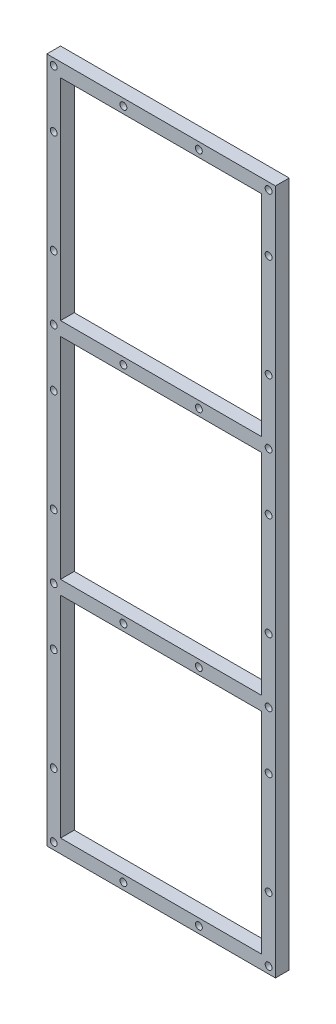
SolidWorks part; units mm, degrees
ref_plane "Front Plane" through (0, 0, 0) normal (0, 0, 1) x (1, 0, 0)
ref_plane "Top Plane" through (0, 0, 0) normal (0, 1, 0) x (1, 0, 0)
ref_plane "Right Plane" through (0, 0, 0) normal (1, 0, 0) x (0, 0, -1)
sketch "Sketch1" plane through (0, 0, 0) normal (0, 0, 1) x (1, 0, 0)
  line L0 (44, 144) -> (44, 52)
  line L9 (-50, -150) -> (50, -150)
  line L10 (-50, -150) -> (-50, 150)
  line L11 (-50, 150) -> (50, 150)
  line L12 (50, -150) -> (50, 150)
  line L15 (-44, -144) -> (44, -144)
  line L16 (-44, -144) -> (-44, -52)
  line L17 (-44, 144) -> (44, 144)
  line L21 (-44, 52) -> (44, 52)
  line L23 (-44, 46) -> (44, 46)
  line L25 (-44, -46) -> (44, -46)
  line L27 (-44, -52) -> (44, -52)
  line L33 (44, 46) -> (44, -46)
  line L34 (-44, 52) -> (-44, 144)
  line L35 (-44, -46) -> (-44, 46)
  line L36 (44, -52) -> (44, -144)
  point P0 (0, 0)
  point P6 (0, 0)
  point P20 (0, 0)
  dimension "D1" = 100
  dimension "D2" = 300
  dimension "D3" = 88
  dimension "D4" = 288
  dimension "D5" = 6
  dimension "D6" = 92
  dimension "D7" = 6
  dimension "D8" = 92
  dimension "D9" = 92
  dimension "D10" = 6
  dimension "D11" = 6
extrude "Boss-Extrude1" add sketch "Sketch1" along normal blind 6
sketch "Sketch2" plane through (0, 0, 6) normal (0, 0, 1) x (1, 0, 0)
  line L0 (-50, 150) -> (-44, 144)
  line L1 (44, 144) -> (50, 150)
  line L2 (44, -144) -> (50, -150)
  line L3 (-44, -144) -> (-50, -150)
  circle A0 centre (-47, 147) radius 1.5
  circle A1 centre (47, 147) radius 1.5
  circle A2 centre (47, 49) radius 1.5
  circle A3 centre (47, -49) radius 1.5
  circle A4 centre (47, -147) radius 1.5
  circle A5 centre (-47, 49) radius 1.5
  circle A6 centre (-47, -49) radius 1.5
  circle A7 centre (-47, -147) radius 1.5
  point P18 (47, 147)
  point P19 (-47, -147)
  point P20 (0, 0)
  dimension "D1" = 94
  dimension "D2" = 294
  dimension "D3" = 2
  dimension "D4" = 4
extrude "Cut-Extrude1" cut sketch "Sketch2" against normal blind 6 contours A0 | A1 | A5 | A2 | A6 | A3 | A7 | A4
sketch "Sketch3" plane through (0, 0, 6) normal (0, 0, 1) x (1, 0, 0)
  line L0 (50, 150) -> (-50, 150) construction
  line L1 (0, 150) -> (0, -150)
  line L2 (-50, -150) -> (50, -150) construction
  circle A0 centre (-47, 122) radius 1.5
  circle A1 centre (-47, 77) radius 1.5
  circle A2 centre (47, 122) radius 1.5
  circle A3 centre (47, 77) radius 1.5
  circle A4 centre (47, 24) radius 1.5
  circle A5 centre (47, -21) radius 1.5
  circle A6 centre (47, -74) radius 1.5
  circle A7 centre (47, -119) radius 1.5
  circle A8 centre (-47, 24) radius 1.5
  circle A9 centre (-47, -21) radius 1.5
  circle A10 centre (-47, -74) radius 1.5
  circle A11 centre (-47, -119) radius 1.5
  circle A12 centre (-16.5, 147) radius 1.5
  circle A13 centre (-16.5, 49) radius 1.5
  circle A14 centre (-16.5, -49) radius 1.5
  circle A15 centre (-16.5, -147) radius 1.5
  circle A16 centre (16.5, -147) radius 1.5
  circle A17 centre (16.5, -49) radius 1.5
  circle A18 centre (16.5, 49) radius 1.5
  circle A19 centre (16.5, 147) radius 1.5
  point P9 (0, 150)
  point P48 (0, 0)
  point P49 (0, 0)
  point P50 (0, 0)
  point P51 (0, 0)
  circle M18 centre (-47, -49) radius 1.5
  dimension "D1" = 28
  dimension "D6" = 16.5
  dimension "D2" = 45
  dimension "D3" = 28
  dimension "D4" = 2
  dimension "D5" = 3
  dimension "D7" = 4
extrude "Cut-Extrude2" cut sketch "Sketch3" against normal blind 10 contours A9 | M18 | A14 | A10 | A11 | A15 | A16 | A7 | A6 | A17 | A5 | A3 | A18 | A12 | A0 | A19 | A1 | A13 | A8 | A4 | A2 | A10 | A11 region at (-47, 122, 6) region at (-47, 77, 6) region at (47, 122, 6) region at (47, 77, 6) region at (47, 24, 6) region at (47, -21, 6) region at (47, -74, 6) region at (47, -119, 6) region at (-47, 24, 6) region at (-47, -21, 6) region at (-47, -74, 6) region at (-47, -119, 6) region at (-16.5, 147, 6) region at (-16.5, 49, 6) region at (-16.5, -49, 6) region at (-16.5, -147, 6) region at (16.5, -147, 6) region at (16.5, -49, 6) region at (16.5, 49, 6) region at (16.5, 147, 6) region at (-47, -49, 6)
